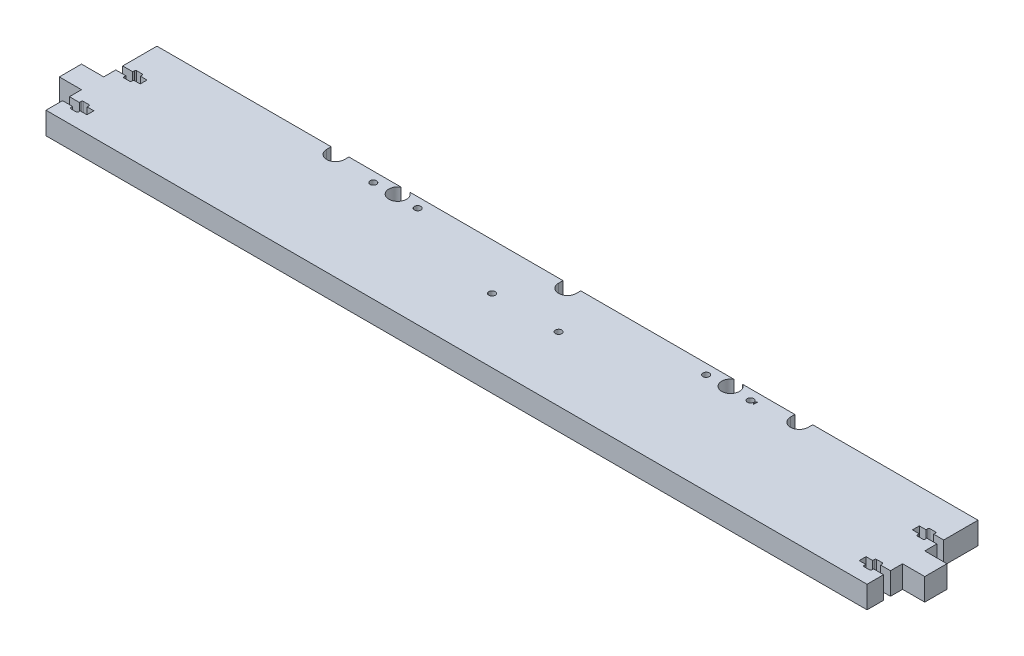
SolidWorks part; units mm, degrees
ref_plane "Front Plane" through (0, 0, 0) normal (0, 0, 1) x (1, 0, 0)
ref_plane "Top Plane" through (0, 0, 0) normal (0, 1, 0) x (1, 0, 0)
ref_plane "Right Plane" through (0, 0, 0) normal (1, 0, 0) x (0, 0, -1)
sketch "Sketch1" plane through (0, 0, 0) normal (0, 1, 0) x (1, 0, 0)
  line L0 (0, 25) -> (0, -25)
  line L1 (-185, 25) -> (0, 25)
  line L2 (-185, 25) -> (-185, -25) construction
  line L3 (-185, -25) -> (0, -25)
  line L4 (-185, -4) -> (-195, -4) construction
  line L5 (-185, 25) -> (0, 0) construction
  line L6 (-185, -25) -> (0, 0) construction
  line L7 (-185, -9) -> (-195, -9)
  line L8 (-195, -9) -> (-195, 1)
  line L9 (-195, 1) -> (-185, 1)
  line L10 (-185, 1) -> (-185, 25)
  line L11 (-185, -9) -> (-185, -25)
  line L47 (0, -25) -> (0, 25) construction
  line L89 (0, -25) -> (0, 25) construction
  point P0 (0, 0)
  dimension "D1" = 185
  dimension "D25" = 25
  dimension "D4" = 50
  dimension "D3" = 21
  dimension "D5" = 10
  dimension "D6" = 10
  dimension "D7" = 5
extrude "MainBody" add sketch "Sketch1" along normal blind 10 contours L3 region at (-93.5428, 0, 0.0428)
sketch "Sketch5" plane through (0, 10, 0) normal (0, 1, 0) x (1, 0, 0)
  line L0 (-185, 8) -> (-174, 8) construction
  line L1 (-185, 1) -> (-185, 25) construction
  line L2 (-185, 9.55) -> (-174, 9.55) construction
  line L3 (-174, 9.55) -> (-174, 6.45) construction
  line L4 (-174, 6.45) -> (-185, 6.45) construction
  line L5 (-185, 9.55) -> (-180.5, 9.55)
  line L6 (-180.5, 9.55) -> (-180.5, 10.35)
  line L7 (-180, 10.85) -> (-177.5, 10.85)
  line L8 (-177, 10.35) -> (-177, 9.55)
  line L9 (-177, 9.55) -> (-174, 9.55)
  line L10 (-174, 9.55) -> (-174, 6.45)
  line L11 (-185, 6.45) -> (-185, 9.55)
  line L12 (-195, -9) -> (-195, 1) construction
  line L13 (-185, 6.45) -> (-174, 6.45) construction
  line L14 (-177, 6.45) -> (-174, 6.45)
  line L15 (-177, 5.65) -> (-177, 6.45)
  line L16 (-180, 5.15) -> (-177.5, 5.15)
  line L17 (-180.5, 6.45) -> (-180.5, 5.65)
  line L18 (-185, 6.45) -> (-180.5, 6.45)
  line L19 (-185, 1) -> (-185, -9) construction
  line L20 (-195, -4) -> (-185, -4) construction
  line L21 (-195, -9) -> (-195, 1) construction
  line L22 (-185, -14.45) -> (-174, -14.45) construction
  line L23 (-174, -14.45) -> (-185, -14.45) construction
  line L24 (-174, -17.55) -> (-174, -14.45) construction
  line L25 (-185, -17.55) -> (-174, -17.55) construction
  line L26 (-185, -16) -> (-174, -16) construction
  line L27 (-185, -14.45) -> (-180.5, -14.45)
  line L28 (-180.5, -14.45) -> (-180.5, -13.65)
  line L29 (-180, -13.15) -> (-177.5, -13.15)
  line L30 (-177, -13.65) -> (-177, -14.45)
  line L31 (-177, -14.45) -> (-174, -14.45)
  line L32 (-185, -14.45) -> (-185, -17.55)
  line L33 (-174, -17.55) -> (-174, -14.45)
  line L34 (-177, -17.55) -> (-174, -17.55)
  line L35 (-177, -18.35) -> (-177, -17.55)
  line L36 (-180, -18.85) -> (-177.5, -18.85)
  line L37 (-180.5, -17.55) -> (-180.5, -18.35)
  line L38 (-185, -17.55) -> (-180.5, -17.55)
  line L39 (-185, 6.45) -> (-174, 6.45) construction
  arc A0 (-177.5, 10.85) -> (-177, 10.35) centre (-177.5, 10.35) cw
  arc A1 (-180.5, 10.35) -> (-180, 10.85) centre (-180, 10.35) cw
  arc A2 (-180.5, 5.65) -> (-180, 5.15) centre (-180, 5.65) ccw
  arc A3 (-177.5, 5.15) -> (-177, 5.65) centre (-177.5, 5.65) ccw
  arc A4 (-177.5, -13.15) -> (-177, -13.65) centre (-177.5, -13.65) cw
  arc A5 (-180.5, -13.65) -> (-180, -13.15) centre (-180, -13.65) cw
  arc A6 (-180.5, -18.35) -> (-180, -18.85) centre (-180, -18.35) ccw
  arc A7 (-177.5, -18.85) -> (-177, -18.35) centre (-177.5, -18.35) ccw
  point P6 (-195, -4)
  point P17 (-177, 10.85)
  point P20 (-180.5, 10.85)
  point P29 (-180.5, 5.15)
  point P30 (-177, 5.15)
  point P61 (-177, -13.15)
  point P62 (-180.5, -13.15)
  point P63 (-180.5, -18.85)
  point P64 (-177, -18.85)
  dimension "D8" = 0.5
  dimension "D1" = 11
  dimension "D2" = 1.55
  dimension "D4" = 3.5
  dimension "D5" = 8
  dimension "D6" = 2.85
  dimension "D7" = 12
extrude "ScrewCutouts" cut sketch "Sketch5" against normal through all
mirror "Mirror1" about plane through (0, 0, 0) normal (1, 0, 0) of "ScrewCutouts", "MainBody"
sketch "Sketch3" plane through (0, 10, 0) normal (0, 1, 0) x (1, 0, 0)
  line L0 (2, 25) -> (2, -25) construction
  line L1 (-185, 25) -> (185, 25) construction
  line L2 (-185, -25) -> (185, -25) construction
  line L3 (-63, 20.5) -> (-83, 20.5) construction
  line L4 (-73, 17.5) -> (-73, 25.5) construction
  line L5 (77, 17.5) -> (77, 25.5) construction
  line L6 (67, 20.5) -> (87, 20.5) construction
  circle A0 centre (-73, 21.5) radius 4
  circle A1 centre (-83, 20.5) radius 1.45
  circle A2 centre (-63, 20.5) radius 1.45
  circle A3 centre (67, 20.5) radius 1.45
  circle A4 centre (87, 20.5) radius 1.45
  circle A5 centre (77, 21.5) radius 4
  dimension "D2" = 8
  dimension "D4" = 2.9
  dimension "D1" = 3.5
  dimension "D5" = 75
  dimension "D6" = 2
  dimension "D3" = 10
  dimension "D7" = 1
extrude "RodCutouts" cut sketch "Sketch3" against normal through all
sketch "Sketch6" plane through (0, 10, 0) normal (0, 1, 0) x (1, 0, 0)
  line L0 (-73, 21.5) -> (77, 21.5) construction
  line L1 (2, 21.5) -> (2, -25) construction
  line L2 (-185, -25) -> (185, -25) construction
  line L3 (17, 4) -> (-13, 4) construction
  line L4 (-71.0635, 25) -> (75.0635, 25) construction
  circle A0 centre (-13, 4) radius 1.45
  circle A1 centre (17, 4) radius 1.45
  point P13 (2, 4)
  dimension "D3" = 21
  dimension "D1" = 2.9
  dimension "D2" = 15
extrude "Cut-Extrude1" cut sketch "Sketch6" against normal through all
sketch "Sketch7" plane through (0, 10, 0) normal (0, 1, 0) x (1, 0, 0)
  line L0 (-73, 21.5) -> (77, 21.5) construction
  line L1 (2, 21.5) -> (2, -25) construction
  line L3 (-102.5, 25) -> (-102.5, 23) construction
  line L4 (-185, 25) -> (-74.9365, 25) construction
  line L5 (-98.5, 25) -> (-98.5, 23)
  line L6 (-106.5, 25) -> (-106.5, 23)
  line L7 (106.5, 25) -> (106.5, 23) construction
  line L8 (102.5, 25) -> (102.5, 23)
  line L9 (110.5, 25) -> (110.5, 23)
  line L12 (-185, -25) -> (185, -25) construction
  arc A0 (-98.5, 25) -> (-106.5, 25) centre (-102.5, 25) ccw
  arc A1 (-106.5, 23) -> (-98.5, 23) centre (-102.5, 23) ccw
  arc A2 (102.5, 25) -> (110.5, 25) centre (106.5, 25) cw
  arc A3 (110.5, 23) -> (102.5, 23) centre (106.5, 23) cw
  point P12 (-102.5, 24)
  point P19 (106.5, 24)
  dimension "D1" = 4
  dimension "D2" = 2
  dimension "D3" = 104.5
extrude "BedAdjustmentScrewCutout" cut sketch "Sketch7" against normal through all
sketch "Sketch8" plane through (0, 10, 0) normal (0, 1, 0) x (1, 0, 0)
  line L0 (88.25, 20.5) -> (89.25, 20.5) construction
  line L1 (88.45, 20.5) -> (88.45, 25) construction
  line L2 (88.25, 20.5) -> (89.25, 21.5)
  line L3 (89.25, 21.5) -> (89.25, 19.5)
  line L4 (88.25, 20.5) -> (89.25, 19.5)
  line L5 (78.9365, 25) -> (102.5, 25) construction
  circle A1 centre (87, 20.5) radius 1.45 construction
  point P9 (89.25, 20.5)
  dimension "D1" = 1
  dimension "D2" = 1
  dimension "D3" = 0.2
extrude "DirectionKey" cut sketch "Sketch8" against normal through all
sketch "Sketch9" plane through (0, 10, 0) normal (0, 1, 0) x (1, 0, 0)
  line L0 (-13, 4) -> (17, 4) construction
  line L1 (2, 4) -> (2, 25) construction
  line L2 (-71.0635, 25) -> (75.0635, 25) construction
  line L3 (2, 27) -> (2, 23) construction
  line L4 (6, 27) -> (6, 23)
  line L5 (-2, 27) -> (-2, 23)
  arc A0 (6, 27) -> (-2, 27) centre (2, 27) ccw
  arc A1 (-2, 23) -> (6, 23) centre (2, 23) ccw
  point P10 (2, 25)
  dimension "D1" = 4
  dimension "D2" = 2
extrude "Cut-Extrude2" cut sketch "Sketch9" against normal through all
equation "\"Y-ROD-SPACING\"=75"
equation "\"Y-BED-OFFSET\"=2"
equation "\"T-SLOT-NUT-FILLET-RADIUS\"=0.5"
equation "\"T-SLOT-SCREW-SHAFT-RADIUS\"=1.55"
equation "\"T-SLOT-SCREW-SHAFT-CUTOUT-LENGTH\"=11"
equation "\"T-SLOT-NUT-DEPTH\"=3.5"
equation "\"T-SLOT-NUT-WIDTH\"=2.85"
equation "\"T-SLOT-NUT-END-DISTANCE\"=8"
equation "\"ACRYLIC-TAB-CUTOUT-SIZE\"=\"ACRYLIC-THICKNESS\"+\"ACRYLIC-TAB-TOLERANCE\"*2"
equation "\"ACRYLIC-M3-HOLE\"=2.9"
equation "\"D1@Sketch5\"=\"T-SLOT-SCREW-SHAFT-CUTOUT-LENGTH\""
equation "\"D2@Sketch5\"=\"T-SLOT-SCREW-SHAFT-RADIUS\""
equation "\"D4@Sketch5\"=\"T-SLOT-NUT-DEPTH\""
equation "\"D5@Sketch5\"=\"T-SLOT-NUT-END-DISTANCE\""
equation "\"D6@Sketch5\"=\"T-SLOT-NUT-WIDTH\""
equation "\"D8@Sketch5\"=\"T-SLOT-NUT-FILLET-RADIUS\""
equation "\"D4@Sketch3\"=\"ACRYLIC-M3-HOLE\""
equation "\"D5@Sketch3\"=\"Y-ROD-SPACING\""
equation "\"D6@Sketch3\"=\"Y-BED-OFFSET\""
equation "\"Y-BED-ROD-INSET\"=3.5"
equation "\"D1@Sketch3\"=\"Y-BED-ROD-INSET\""
equation "\"SMOOTHROD-CAP-SCREW-DISTANCE\"=20"
equation "\"D3@Sketch3\"=\"SMOOTHROD-CAP-SCREW-DISTANCE\"/2"
equation "\"ACRYLIC-TAB-WIDTH\"=\"ACRYLIC-THICKNESS\""
equation "\"FRAME-WIDTH-INNER\"=370"
equation "\"D6@Sketch1\"=\"ACRYLIC-TAB-WIDTH\""
equation "\"D5@Sketch1\"=\"ACRYLIC-TAB-WIDTH\""
equation "\"D1@Sketch1\"=\"FRAME-WIDTH-INNER\"/2"
equation "\"X-ROD-SPACING\"=45"
equation "\"Z-ROD-SPACING\"=17.5"
equation "\"ACRYLIC-THICKNESS\"=10"
equation "\"ACRYLIC-THICKNESS2\"=4.5"
equation "\"NEMA17-HOLE-SPACING\"=31"
equation "\"NEMA17-CENTRAL-CUTOUT\"=22.5"
equation "\"Z-BRACKET-REACH\"=55"
equation "\"TOP-BRACKET-SPACING\"=40"
equation "\"SMOOTHROD-X-LENGTH\"=350"
equation "\"SMOOTHROD-Y-LENGTH\"=350"
equation "\"SMOOTHROD-Z-LENGTH\"=350"
equation "\"SMOOTHROD-TIGHTENING-HEADROOM\"=.25"
equation "\"LEADSCREW-Z-LENGTH\"=300"
equation "\"SCREW-LENGTH-FRAME\"=\"ACRYLIC-THICKNESS\" + 10"
equation "\"SCREW-HEAD-RADIUS\"=6"
equation "\"PRINTED-X-SMOOTHROD-DIAMETER\"=8.8"
equation "\"PRINTED-X-SMOOTHROD-CUTOUT\"=10"
equation "\"PRINTED-X-BASE-HEIGHT\"=10"
equation "\"PRINTED-LM8UU-CUTOUT-SIZE\"=15.5"
equation "\"PRINTED-LM8UU-CUTOUT-LENGTH\"=24.5"
equation "\"PRINTED-X-IDLER-HEIGHT\"=16"
equation "\"PSU-MOUNTING-WIDTH\"=95"
equation "\"PSU-MOUNTING-HEIGHT\"=177"
equation "\"D1@MainBody\"=\"ACRYLIC-THICKNESS\""
equation "\"D7@Sketch1\"=\"ACRYLIC-TAB-WIDTH\"/2"
equation "\"D1@Sketch6\"=\"ACRYLIC-M3-HOLE\""
equation "\"Y-BELT-TO-ROD-DISTANCE\"=20"
equation "\"Y-BED-SCREW-SPACING\"=209"
equation "\"Z-ROD-INSET\"=13.5"
equation "\"SPOOL-HOLDER-ROD-SPACING\"=150"
equation "\"D3@Sketch7\"=\"Y-BED-SCREW-SPACING\"/2"
equation "\"Y-BED-SCREW-CUTOUT-SLOT-HEIGHT\"=2"
equation "\"D2@Sketch7\"=\"Y-BED-SCREW-CUTOUT-SLOT-HEIGHT\""
equation "\"ACRYLIC-TAB-TOLERANCE\"=-.05"
equation "\"SCREW-LENGTH-MOTOR\"=\"ACRYLIC-THICKNESS\" + 5"
equation "\"SCREW-LENGTH-EXTRUDER\"=28"
equation "\"PRINTED-M3-HOLE\"=3.5"
equation "\"ACRYLIC-X-CARRIAGE-WIDTH\"=55"
equation "\"ACRYLIC-X-CARRIAGE-HEIGHT\"=75"
equation "\"ACRYLIC-X-CARRIAGE-LM8UU-CUTOUT-WIDTH\"=24.25"
equation "\"ACRYLIC-X-CARRIAGE-LM8UU-CUTOUT-HEIGHT\"=11.0"
equation "\"ACRYLIC-X-CARRIAGE-SCREW-SPACING-X\"=15"
equation "\"ACRYLIC-X-CARRIAGE-SCREW-SPACING-Y\"=33"
equation "\"ACRYLIC-X-CARRIAGE-CENTER-TAB-SPACING\"=14"
equation "\"ACRYLIC-X-CARRIAGE-EXTRUDER-OFFSET\"=26"
equation "\"ACRYLIC-X-CARRIAGE-EXTRUDER-ANGLE\"=90"
equation "\"ACRYLIC-X-CARRIAGE-EXTRUDER-SHELF-DEPTH\"=\"ACRYLIC-X-CARRIAGE-EXTRUDER-OFFSET\" + 28"
equation "\"ACRYLIC-X-CARRIAGE-EXTRUDER-BRACE-SPACING\"=23"
equation "\"ACRYLIC-X-CARRIAGE-EXTRUDER-BRACE-TAB-OFFSET\"=20"
equation "\"ACRYLIC-X-CARRIAGE-EXTRUDER-BRACE-HEIGHT\"=35"
equation "\"ACRYLIC-X-CARRIAGE-EXTRUDER-BRACE-SCREW-SPACING\"=22"
equation "\"ACRYLIC-X-CARRIAGE-DUAL-WIDTH-MULTIPLIER\"=1.65"
equation "\"ACRYLIC-X-CARRIAGE-DUAL-HOTEND-SPACING\"=42"
equation "\"ACRYLIC-X-CARRIAGE-DUAL-WIDTH\"=75"
equation "\"ACRYLIC-X-CARRIAGE-DUAL-HOTEND-SEPARATION\"=36"
equation "\"ACRYLIC-X-CARRIAGE-DUAL-MOUNT-PLATE-DEPTH\"=75"
equation "\"ACRYLIC-X-CARRIAGE-DUAL-MOUNT-BRACE-WIDTH\"=33"
equation "\"ACRYLIC-X-CARRIAGE-DUAL-MOUNT-SCREW-WIDTH\"=40"
equation "\"BLOWER-FAN-WIDTH\"=15"
equation "\"D2@Sketch9\"=\"Y-BED-SCREW-CUTOUT-SLOT-HEIGHT\""
